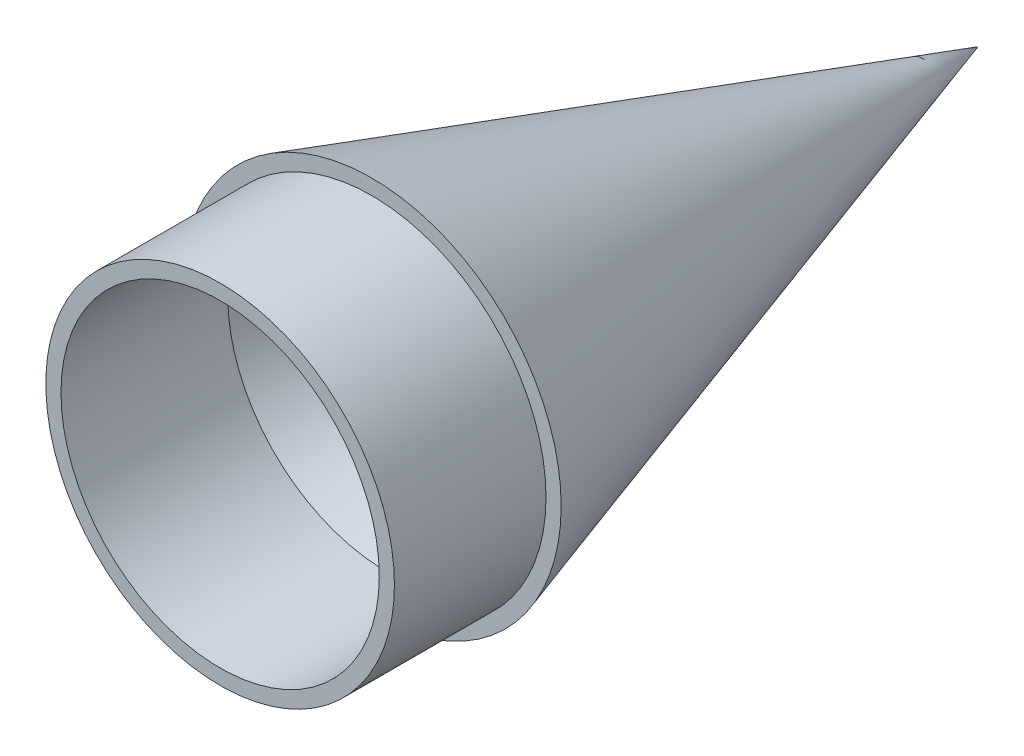
SolidWorks part; units mm, degrees
material "ABS"
ref_plane "Спереди" through (0, 0, 0) normal (0, 0, 1) x (1, 0, 0)
ref_plane "Сверху" through (0, 0, 0) normal (0, 1, 0) x (1, 0, 0)
ref_plane "Справа" through (0, 0, 0) normal (1, 0, 0) x (0, 0, -1)
sketch "Эскиз1" plane through (0, 0, 0) normal (0, 1, 0) x (1, 0, 0)
  line L0 (0, 0) -> (0, 80) construction
  line L1 (0, 0) -> (-25, 0) construction
  line L2 (0, 80) -> (-25, 0)
  line L3 (-25, 0) -> (-23, 0)
  line L4 (-23, 0) -> (-23, -20)
  line L5 (-21.7437, -20) -> (0, -20)
  line L6 (0, -20) -> (0, 80)
  line L7 (-21.7437, -20) -> (-23, -20)
  dimension "D1" = 25
  dimension "D2" = 2
  dimension "D3" = 20
  dimension "D4" = 23
  dimension "D5" = 100
revolve "Повернуть1" add sketch "Эскиз1" angle 360 about L6
shell "Оболочка1" thickness 2 removed face at (23, 0, 20)
